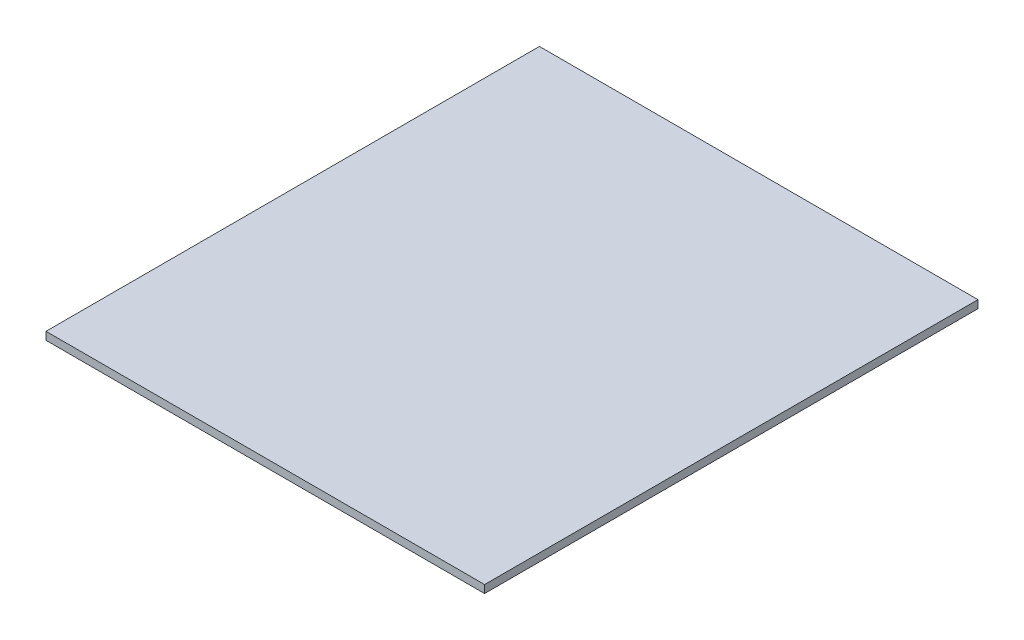
SolidWorks part; units mm, degrees
material "Maple"
ref_plane "Front Plane" through (0, 0, 0) normal (0, 0, 1) x (1, 0, 0)
ref_plane "Top Plane" through (0, 0, 0) normal (0, 1, 0) x (1, 0, 0)
ref_plane "Right Plane" through (0, 0, 0) normal (1, 0, 0) x (0, 0, -1)
sketch "Sketch1" plane through (0, 0, 0) normal (0, 1, 0) x (1, 0, 0)
  line L1 (0, 0) -> (355.6, 0)
  line L2 (0, 0) -> (0, 400.05)
  line L3 (0, 400.05) -> (355.6, 400.05)
  line L4 (355.6, 0) -> (355.6, 400.05)
  dimension "D1" = 400.05
  dimension "D2" = 355.6
extrude "Boss-Extrude1" add sketch "Sketch1" along normal blind 6.35
